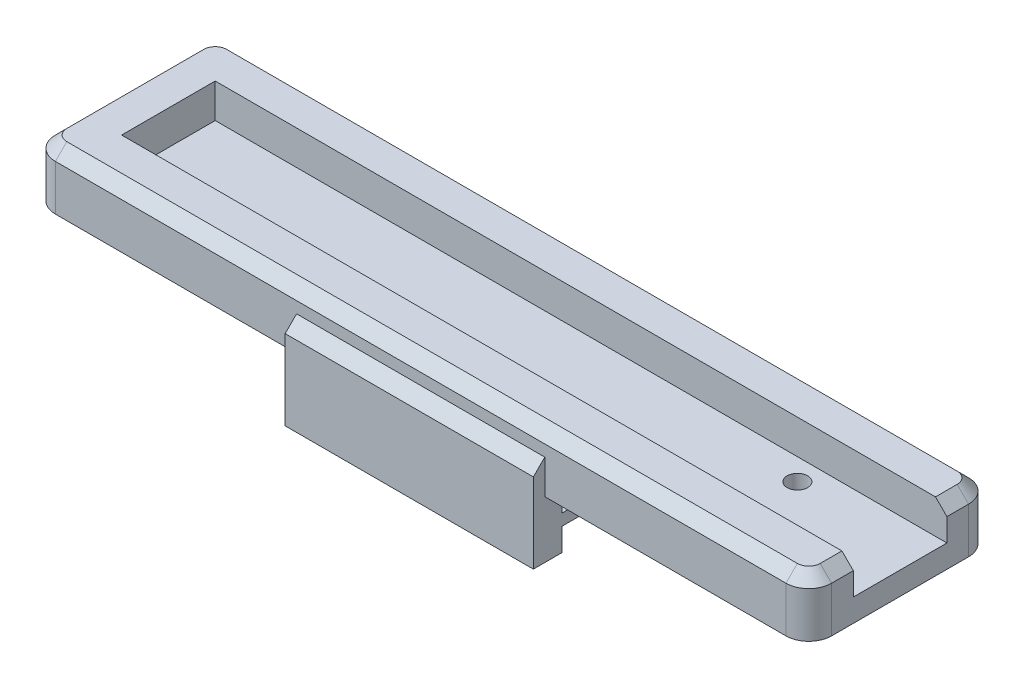
SolidWorks part; units mm, degrees
ref_plane "Front Plane" through (0, 0, 0) normal (0, 0, 1) x (1, 0, 0)
ref_plane "Top Plane" through (0, 0, 0) normal (0, 1, 0) x (1, 0, 0)
ref_plane "Right Plane" through (0, 0, 0) normal (1, 0, 0) x (0, 0, -1)
sketch "Sketch2" plane through (0, 0, 0) normal (0, 1, 0) x (1, 0, 0)
  line L1 (-34, 8) -> (34, 8)
  line L2 (-34, 8) -> (-34, -8)
  line L3 (-34, -8) -> (34, -8)
  line L4 (34, 8) -> (34, -8)
  line L5 (-34, 8) -> (34, -8) construction
  line L6 (-34, -8) -> (34, 8) construction
  line L7 (-30, 4) -> (30, 4) construction
  line L8 (-30, 4) -> (-30, -4) construction
  line L9 (-30, -4) -> (30, -4) construction
  line L10 (30, 4) -> (30, -4) construction
  line L11 (-30, 4) -> (30, -4) construction
  line L12 (-30, -4) -> (30, 4) construction
  point P0 (0, 0)
  point P5 (0, 0)
  dimension "D1" = 60
  dimension "D2" = 8
  dimension "D3" = 4
  dimension "D4" = 4
extrude "Boss-Extrude1" add sketch "Sketch2" along normal blind 2
sketch "Sketch3" plane through (0, 2, 0) normal (0, 1, 0) x (1, 0, 0)
  line L1 (-30.1, 4.1) -> (30.1, 4.1)
  line L2 (-30.1, 4.1) -> (-30.1, -4.1)
  line L3 (-30.1, -4.1) -> (30.1, -4.1)
  line L4 (30.1, 4.1) -> (30.1, -4.1)
  line L5 (-30.1, 4.1) -> (30.1, -4.1) construction
  line L6 (-30.1, -4.1) -> (30.1, 4.1) construction
  line L7 (-34, -8) -> (34, -8)
  line L8 (-34, -8) -> (-34, 8)
  line L9 (-34, 8) -> (34, 8)
  line L10 (34, -8) -> (34, 8)
  line L11 (-34, -8) -> (34, 8) construction
  line L12 (-34, 8) -> (34, -8) construction
  point P0 (0, 0)
  point P5 (0, 0)
  dimension "D1" = 8.2
  dimension "D2" = 60.2
extrude "Boss-Extrude2" add sketch "Sketch3" along normal blind 3
sketch "Sketch4" plane through (0, 2, 0) normal (0, 1, 0) x (1, 0, 0)
  line L0 (-30.1, 4.1) -> (-30.1, -4.1) construction
  line L1 (30.1, -4.1) -> (30.1, 4.1) construction
  line L2 (-30.1, -4.1) -> (30.1, -4.1) construction
  line L3 (30.1, 4.1) -> (-30.1, 4.1) construction
  circle A0 centre (-24.8, -2.2) radius 0.9
  circle A1 centre (22.8, 2.2) radius 0.9
  dimension "D1" = 1.8
  dimension "D2" = 1.8
  dimension "D3" = 5.3
  dimension "D4" = 7.3
  dimension "D5" = 1.9
  dimension "D6" = 1.9
extrude "Cut-Extrude1" cut sketch "Sketch4" against normal through all
sketch "Sketch5" plane through (0, 0, 0) normal (0, -1, 0) x (1, 0, 0)
  line L1 (-10.8716, 9) -> (10.8716, 9)
  line L2 (-10.8716, 9) -> (-10.8716, -9)
  line L3 (-10.8716, -9) -> (10.8716, -9)
  line L4 (10.8716, 9) -> (10.8716, -9)
  line L5 (-10.8716, 9) -> (10.8716, -9) construction
  line L6 (-10.8716, -9) -> (10.8716, 9) construction
  line L7 (-8.8716, 6.2692) -> (8.8716, 6.2692) construction
  line L8 (-8.8716, 6.2692) -> (-8.8716, -6.2692) construction
  line L9 (-8.8716, -6.2692) -> (8.8716, -6.2692) construction
  line L10 (8.8716, 6.2692) -> (8.8716, -6.2692) construction
  line L11 (-8.8716, 6.2692) -> (8.8716, -6.2692) construction
  line L12 (-8.8716, -6.2692) -> (8.8716, 6.2692) construction
  point P0 (0, 0)
  point P5 (0, 0)
  dimension "D1" = 18
  dimension "D2" = 2
extrude "Boss-Extrude3" add sketch "Sketch5" along normal blind 5
sketch "Sketch6" plane through (-10.8716, 0, 0) normal (-1, 0, 0) x (0, 0, 1)
  line L0 (9, -5) -> (-9, -5) construction
  line L1 (-6.5, 0) -> (6.5, 0)
  line L2 (-6.5, 0) -> (-6.5, -5)
  line L3 (-6.5, -5) -> (6.5, -5)
  line L4 (6.5, 0) -> (6.5, -5)
  line L5 (-6.5, 0) -> (6.5, -5) construction
  line L6 (-6.5, -5) -> (6.5, 0) construction
  line L7 (-8, 0) -> (-9, 0) construction
  point P0 (0, -2.5)
  dimension "D1" = 13
extrude "Cut-Extrude3" cut sketch "Sketch6" against normal up to surface (21.7431 mm away) up to face at (10.8716, -1.6667, 0)
sketch "Sketch7" plane through (-10.8716, 0, 0) normal (-1, 0, 0) x (0, 0, 1)
  line L5 (-6.5, 0) -> (-6.5, -5) construction
  line L6 (-6.5, -2) -> (-5, -2)
  line L7 (-6.5, -2) -> (-6.5, -3)
  line L8 (-6.5, -3) -> (-5, -3)
  line L9 (-5, -2) -> (-5, -3)
  line L10 (6.5, -5) -> (6.5, 0) construction
  line L11 (6.5, -2) -> (5, -2)
  line L12 (6.5, -2) -> (6.5, -3)
  line L13 (6.5, -3) -> (5, -3)
  line L14 (5, -2) -> (5, -3)
  line L15 (-9, -2.5) -> (9, -2.5) construction
  line L16 (-9, -5) -> (-9, 0) construction
  line L17 (9, -5) -> (9, 0) construction
  point P18 (5, -2.5)
  point P19 (-5, -2.5)
  dimension "D1" = 1.5
  dimension "D2" = 1.5
  dimension "D3" = 1
  dimension "D4" = 1
extrude "Boss-Extrude4" add sketch "Sketch7" against normal up to surface (21.7431 mm away) up to face at (10.8716, -2, 7.8)
chamfer "Chamfer1" distance 3 angle 45 2 edges at (0, 0, 8) (0, 0, -8)
sketch "Sketch8" plane through (0, 5, 0) normal (0, 1, 0) x (1, 0, 0)
  line L0 (34, -8) -> (34, 8) construction
  line L1 (30.1, -4.1) -> (34, -4.1)
  line L2 (30.1, -4.1) -> (30.1, 4.1)
  line L3 (30.1, 4.1) -> (34, 4.1)
  line L4 (34, -4.1) -> (34, 4.1)
  line L5 (30.1, 4.1) -> (-30.1, 4.1) construction
extrude "Cut-Extrude4" cut sketch "Sketch8" against normal up to surface (3 mm away) up to face at (-24.8, 2, 3.1)
fillet "Fillet1" radius 2 4 edges at (34, 2.5, 8) (34, 2.5, -8) (-34, 2.5, -8) (-34, 2.5, 8)
chamfer "Chamfer2" distance 1 angle 45 9 edges at (34, 5, 5.05) (33.4142, 5, 7.4142) (0, 5, 8) (-33.4142, 5, 7.4142) (34, 5, -5.05) (-34, 5, 0) (33.4142, 5, -7.4142) (-33.4142, 5, -7.4142) (0, 5, -8)
